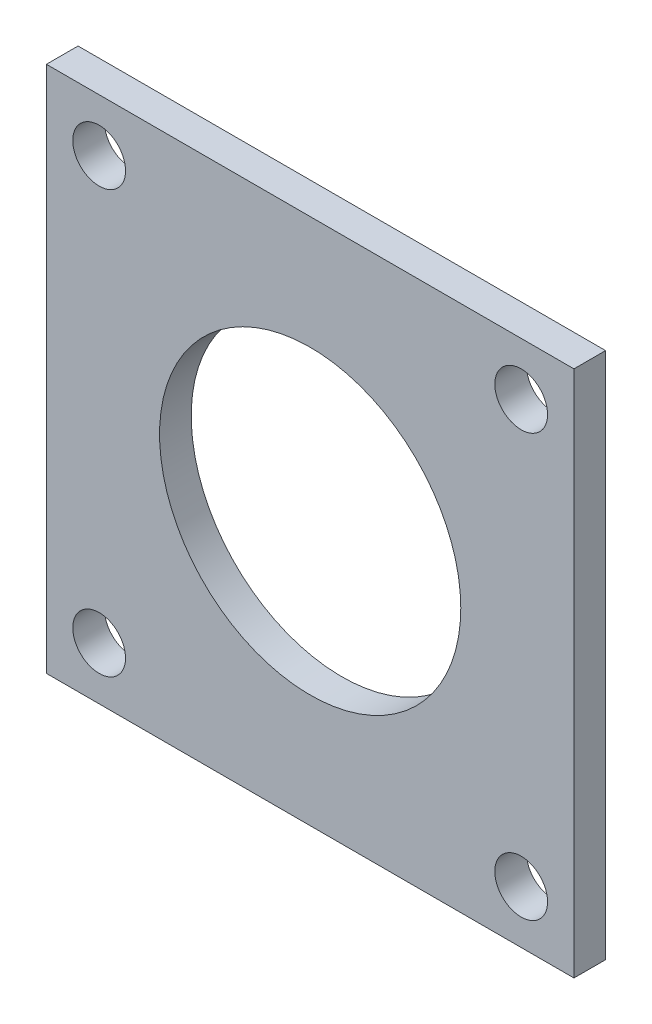
SolidWorks part; units mm, degrees
ref_plane "Front Plane" through (0, 0, 0) normal (0, 0, 1) x (1, 0, 0)
ref_plane "Top Plane" through (0, 0, 0) normal (0, 1, 0) x (1, 0, 0)
ref_plane "Right Plane" through (0, 0, 0) normal (1, 0, 0) x (0, 0, -1)
sketch "Sketch1" plane through (0, 0, 0) normal (0, 0, 1) x (1, 0, 0)
  line L1 (0, 0) -> (50, 0)
  line L2 (0, 0) -> (0, 50)
  line L3 (0, 50) -> (50, 50)
  line L4 (50, 0) -> (50, 50)
  dimension "D1" = 50
  dimension "D2" = 50
extrude "Boss-Extrude1" add sketch "Sketch1" along normal blind 3 contours L3 L4 L1 L2
sketch "Sketch2" plane through (0, 0, 3) normal (0, 0, 1) x (1, 0, 0)
  line L0 (25, 50) -> (25, 0) construction
  line L1 (0, 50) -> (50, 50) construction
  line L2 (0, 0) -> (50, 0) construction
  line L3 (0, 25) -> (50, 25) construction
  line L4 (0, 0) -> (0, 50) construction
  line L5 (50, 0) -> (50, 50) construction
  circle A0 centre (25, 25) radius 14.275
  circle A1 centre (5, 45) radius 2.5
  circle A2 centre (5, 5) radius 2.5
  circle A3 centre (45, 45) radius 2.5
  circle A4 centre (45, 5) radius 2.5
  dimension "D1" = 28.55
  dimension "D2" = 5
  dimension "D3" = 5
  dimension "D4" = 5
  dimension "D5" = 5
  dimension "D6" = 5
  dimension "D7" = 5
  dimension "D8" = 5
  dimension "D9" = 5
  dimension "D10" = 5
  dimension "D11" = 5
  dimension "D12" = 5
  dimension "D13" = 5
extrude "Cut-Extrude1" cut sketch "Sketch2" against normal blind 3
